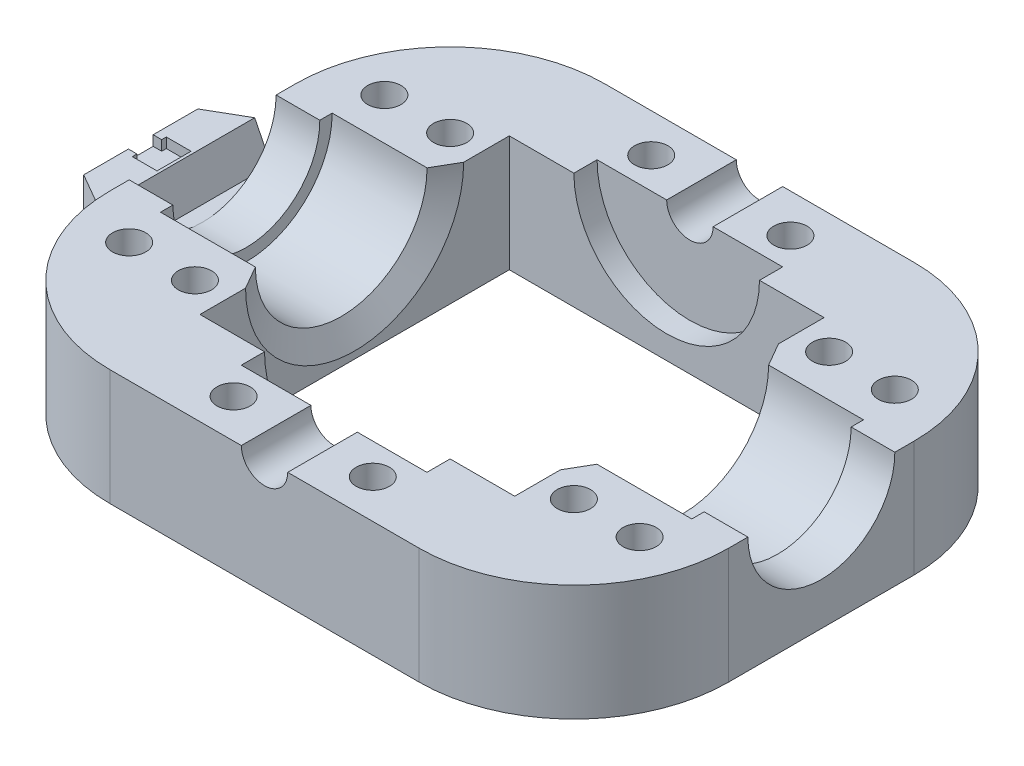
SolidWorks part; units mm, degrees
ref_plane "Спереди" through (0, 0, 0) normal (0, 0, 1) x (1, 0, 0)
ref_plane "Сверху" through (0, 0, 0) normal (0, 1, 0) x (1, 0, 0)
ref_plane "Справа" through (0, 0, 0) normal (1, 0, 0) x (0, 0, -1)
sketch "Sketch1" plane through (0, 0, 0) normal (0, 1, 0) x (1, 0, 0)
  line L1 (40, -32) -> (-40, -32)
  line L2 (40, -32) -> (40, 32)
  line L3 (40, 32) -> (-40, 32)
  line L4 (-40, -32) -> (-40, 32)
  line L5 (40, -32) -> (-40, 32) construction
  line L6 (40, 32) -> (-40, -32) construction
  line L7 (20.35, -20) -> (-20.35, -20)
  line L8 (20.35, -20) -> (20.35, 20)
  line L9 (20.35, 20) -> (-20.35, 20)
  line L10 (-20.35, -20) -> (-20.35, 20)
  line L11 (20.35, -20) -> (-20.35, 20) construction
  line L12 (20.35, 20) -> (-20.35, -20) construction
  point P0 (0, 0)
  point P6 (0, 0)
  dimension "D1" = 80
  dimension "D2" = 64
  dimension "D3" = 40
  dimension "D4" = 40.7
extrude "Boss-Extrude1" add sketch "Sketch1" along normal blind 15
sketch "Sketch3" plane through (0, 15, 0) normal (0, 1, 0) x (1, 0, 0)
  line L0 (-20.35, 0) -> (-40, 0) construction
  line L1 (-20.35, 20) -> (-20.35, -20) construction
  line L2 (-40, 32) -> (-40, -32) construction
  line L3 (20.35, 0) -> (40, 0) construction
  line L4 (20.35, -20) -> (20.35, 20) construction
  line L5 (40, -32) -> (40, 32) construction
  line L10 (20.35, -11.1) -> (34.35, -11.1)
  line L11 (20.35, -11.1) -> (20.35, 0)
  line L12 (20.35, 0) -> (34.35, 0)
  line L13 (34.35, -11.1) -> (34.35, 0)
  line L14 (20.35, -11.1) -> (34.35, 0) construction
  line L15 (20.35, 0) -> (34.35, -11.1) construction
  line L16 (-34.35, -11.1) -> (-20.35, -11.1)
  line L17 (-34.35, -11.1) -> (-34.35, 0)
  line L18 (-34.35, 0) -> (-20.35, 0)
  line L19 (-20.35, -11.1) -> (-20.35, 0)
  line L20 (-34.35, -11.1) -> (-20.35, 0) construction
  line L21 (-34.35, 0) -> (-20.35, -11.1) construction
  point P18 (27.35, -5.55)
  point P23 (-27.35, -5.55)
  dimension "D1" = 14
  dimension "D2" = 11.1
revolve "Cut-Revolve1" cut sketch "Sketch3" angle 360 about L12
sketch "Sketch4" plane through (40, 0, 0) normal (1, 0, 0) x (0, 0, -1)
  line L0 (-32, 15) -> (32, 15) construction
  circle A0 centre (0, 15) radius 9.5
  dimension "D1" = 19
extrude "Cut-Extrude2" cut sketch "Sketch4" against normal through all
sketch "Sketch5" plane through (0, 0, 32) normal (0, 0, 1) x (1, 0, 0)
  line L0 (-40, 15) -> (40, 15) construction
  circle A0 centre (0, 15) radius 3
  dimension "D1" = 6
extrude "Cut-Extrude3" cut sketch "Sketch5" against normal through all
sketch "Sketch8" plane through (0, 15, 0) normal (0, 1, 0) x (1, 0, 0)
  line L1 (-24.5, -16.5) -> (24.5, -16.5) construction
  line L2 (-24.5, -16.5) -> (-24.5, 16.5) construction
  line L3 (-24.5, 16.5) -> (24.5, 16.5) construction
  line L4 (24.5, -16.5) -> (24.5, 16.5) construction
  line L5 (-24.5, -16.5) -> (24.5, 16.5) construction
  line L6 (-24.5, 16.5) -> (24.5, -16.5) construction
  line L7 (-9, 27) -> (9, 27) construction
  line L8 (-9, 27) -> (-9, -27) construction
  line L9 (-9, -27) -> (9, -27) construction
  line L10 (9, 27) -> (9, -27) construction
  line L11 (-9, 27) -> (9, -27) construction
  line L12 (-9, -27) -> (9, 27) construction
  line L13 (33, -16.5) -> (-33, -16.5) construction
  line L14 (33, -16.5) -> (33, 16.5) construction
  line L15 (33, 16.5) -> (-33, 16.5) construction
  line L16 (-33, -16.5) -> (-33, 16.5) construction
  line L17 (33, -16.5) -> (-33, 16.5) construction
  line L18 (33, 16.5) -> (-33, -16.5) construction
  circle A0 centre (24.5, 16.5) radius 2.15
  circle A1 centre (24.5, -16.5) radius 2.15
  circle A2 centre (-24.5, -16.5) radius 2.15
  circle A3 centre (-24.5, 16.5) radius 2.15
  circle A4 centre (9, -27) radius 2.15
  circle A5 centre (-9, -27) radius 2.15
  circle A6 centre (-9, 27) radius 2.15
  circle A7 centre (9, 27) radius 2.15
  circle A8 centre (-33, 16.5) radius 2.15
  circle A9 centre (-33, -16.5) radius 2.15
  circle A10 centre (33, -16.5) radius 2.15
  circle A11 centre (33, 16.5) radius 2.15
  point P0 (0, 0)
  point P10 (0, 0)
  point P16 (0, 0)
  dimension "D3" = 4.3
  dimension "D1" = 33
  dimension "D2" = 49
  dimension "D4" = 18
  dimension "D5" = 54
  dimension "D6" = 66
extrude "Cut-Extrude6" cut sketch "Sketch8" against normal through all
fillet "Fillet1" radius 20 4 edges at (-40, 7.5, 32) (-40, 7.5, -32) (40, 7.5, -32) (40, 7.5, 32)
chamfer "Chamfer1" distance 3 angle 30 2 edges at (-20.35, 3.9, 0) (20.35, 3.9, 0) first distance on face at (-20.35, 8.15, 0) first distance on face at (20.35, 8.15, 0)
sketch "Sketch9" plane through (0, 15, 0) normal (0, 1, 0) x (1, 0, 0)
  line L0 (0, 29.8714) -> (0, -31.0419) construction
  line L1 (-3, 20) -> (-20.35, 20) construction
  line L2 (-12, -23) -> (0, -23)
  line L3 (-12, -23) -> (-12, -20)
  line L4 (-12, -20) -> (0, -20)
  line L5 (0, -23) -> (0, -20)
  line L6 (-12, -23) -> (0, -20) construction
  line L7 (-12, -20) -> (0, -23) construction
  line L8 (-12, 20) -> (0, 20)
  line L9 (-12, 20) -> (-12, 23)
  line L10 (-12, 23) -> (0, 23)
  line L11 (0, 20) -> (0, 23)
  line L12 (-12, 20) -> (0, 23) construction
  line L13 (-12, 23) -> (0, 20) construction
  line L14 (-20.35, -20) -> (-3, -20) construction
  point P3 (-6, -21.5)
  point P8 (-6, 21.5)
  dimension "D1" = 3
  dimension "D2" = 12
revolve "Cut-Revolve2" cut sketch "Sketch9" angle 360 about L0
sketch "Sketch10" plane through (-40, 0, 0) normal (-1, 0, 0) x (0, 0, 1)
  line L0 (-9.5, 15) -> (9.5, 15) construction
  line L1 (0, 15) -> (0, 0) construction
  line L2 (-12, 0) -> (12, 0) construction
  line L4 (12, 5.5) -> (-12, 5.5)
  line L5 (12, 5.5) -> (12, 0)
  line L6 (12, 0) -> (-12, 0)
  line L7 (-12, 5.5) -> (-12, 0)
  line L8 (12, 5.5) -> (-12, 0) construction
  line L9 (12, 0) -> (-12, 5.5) construction
  arc A0 (-9.5, 15) -> (9.5, 15) centre (0, 15) ccw construction
  point P8 (0, 2.75)
extrude "Boss-Extrude2" add sketch "Sketch10" along normal blind 8
sketch "Sketch12" plane through (-40, 0, 0) normal (-1, 0, 0) x (0, 0, 1)
  line L0 (-9.5, 15) -> (9.5, 15) construction
  line L1 (0, 15) -> (0, 0) construction
  line L3 (12, 9.2) -> (-12, 9.2)
  line L4 (12, 9.2) -> (12, 5.5)
  line L5 (12, 5.5) -> (-12, 5.5)
  line L6 (-12, 9.2) -> (-12, 5.5)
  line L7 (12, 9.2) -> (-12, 5.5) construction
  line L8 (12, 5.5) -> (-12, 9.2) construction
  point P7 (0, 7.35)
  dimension "D1" = 5.8
extrude "Boss-Extrude3" add sketch "Sketch12" along normal up to surface (8 mm away) from offset 2 up to face at (-48, 2.75, 0)
sketch "Sketch13" plane through (0, 9.2, 0) normal (0, 1, 0) x (1, 0, 0)
  line L0 (-42, 0) -> (-48, 0) construction
  line L1 (-42, -12) -> (-42, 12) construction
  line L2 (-48, 12) -> (-48, -12) construction
  line L3 (-46.9, 2.2) -> (-46.9, 1.6)
  line L4 (-46.9, -2.2) -> (-43.7, -2.2)
  line L5 (-46.9, 1.6) -> (-48, 1.6)
  line L6 (-46.9, 2.2) -> (-43.7, 2.2)
  line L7 (-43.7, -2.2) -> (-43.7, 2.2)
  line L8 (-46.9, -2.2) -> (-43.7, 2.2) construction
  line L9 (-46.9, 2.2) -> (-43.7, -2.2) construction
  line L10 (-46.9, -2.2) -> (-46.9, -1.6)
  line L11 (-46.9, -1.6) -> (-48, -1.6)
  line L12 (-48, -1.6) -> (-48, -12)
  line L13 (-48, -12) -> (-42, -12)
  line L14 (-42, -12) -> (-42, 12)
  line L15 (-42, 12) -> (-48, 12)
  line L16 (-48, 12) -> (-48, 1.6)
  point P6 (-45.3, 0)
  dimension "D1" = 3.2
  dimension "D2" = 4.4
  dimension "D3" = 3.2
  dimension "D4" = 2.7
extrude "Boss-Extrude4" add sketch "Sketch13" along normal blind 1.3
chamfer "Chamfer2" distance 5 angle 15 1 edges at (-42, 10.5, 0) first distance on face at (-42, 8, 0)
chamfer "Chamfer3" distance 8 angle 30 2 edges at (-48, 5.25, 12) (-48, 5.25, -12) first distance on face at (-43.5566, 5.3333, 12) first distance on face at (-43.5566, 5.3333, -12)
